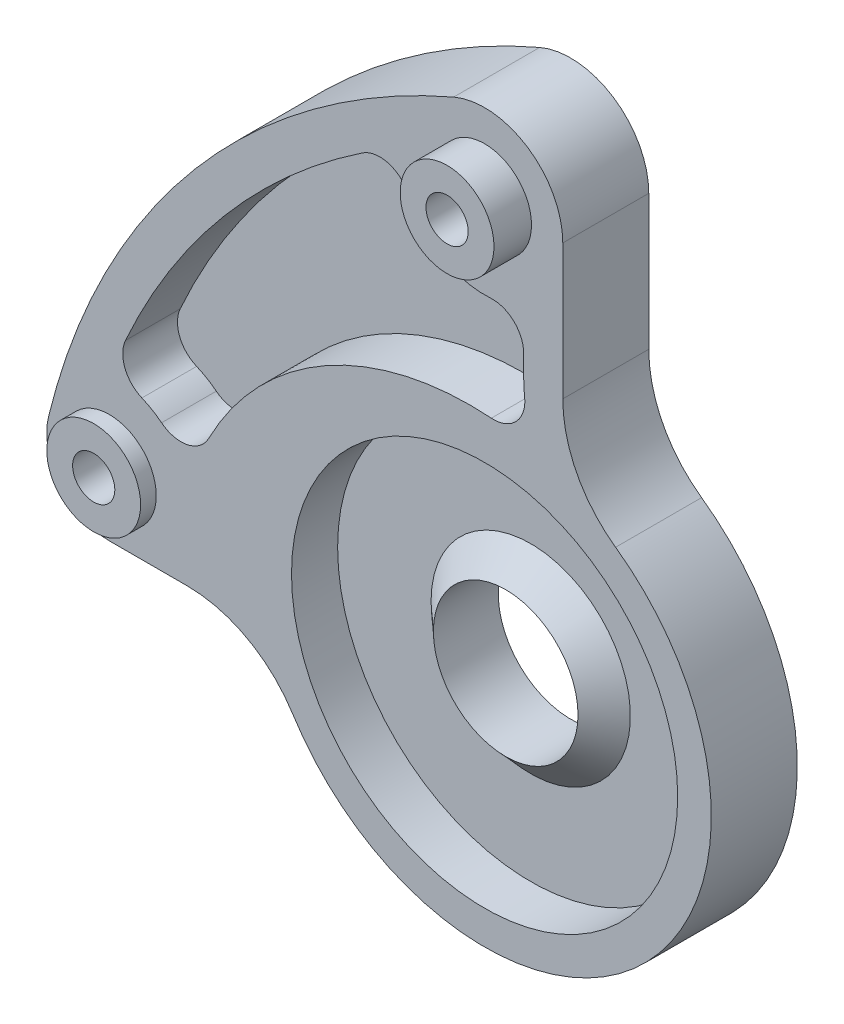
SolidWorks part; units mm, degrees
ref_plane "Front Plane" through (0, 0, 0) normal (0, 0, 1) x (1, 0, 0)
ref_plane "Top Plane" through (0, 0, 0) normal (0, 1, 0) x (1, 0, 0)
ref_plane "Right Plane" through (0, 0, 0) normal (1, 0, 0) x (0, 0, -1)
ref_plane "Plane1" through (0, 0, 5.5) normal (0, 0, 1) x (1, 0, 0)
sketch "Sketch1" plane through (0, 0, 5.5) normal (0, 0, 1) x (1, 0, 0)
  line L0 (5, 18.3644) -> (5, 27)
  line L1 (-24, -4) -> (-19.0329, -4)
  arc A0 (8.3778, 11.8348) -> (5, 18.3644) centre (13, 18.3644) cw
  arc A1 (5, 27) -> (-1.9784, 31.5919) centre (0, 27) ccw
  arc A2 (-1.9784, 31.5919) -> (-27.8856, 0.9498) centre (15.8274, -9.7355) ccw
  arc A3 (-27.8856, 0.9498) -> (-24, -4) centre (-24, 0) ccw
  arc A4 (-19.0329, -4) -> (-12.2656, -7.7333) centre (-19.0329, -12) cw
  arc A5 (-12.2656, -7.7333) -> (8.3778, 11.8348) centre (0, 0) ccw
extrude "Boss-Extrude1" add sketch "Sketch1" against normal blind 5.5
sketch "Sketch2" plane through (0, 0, 5.5) normal (0, 0, 1) x (1, 0, 0)
  circle A0 centre (0, 27) radius 3
  dimension "D1" = 6
extrude "Boss-Extrude2" add sketch "Sketch2" along normal blind 2.4
sketch "Sketch3" plane through (0, 0, 5.5) normal (0, 0, 1) x (1, 0, 0)
  circle A0 centre (-24, 0) radius 3
  dimension "D1" = 6
extrude "Boss-Extrude3" add sketch "Sketch3" along normal blind 1
sketch "Sketch4" plane through (0, 0, 0) normal (0, 0, -1) x (-1, 0, 0)
  circle A0 centre (0, 0) radius 4.625
  dimension "D1" = 9.25
extrude "Cut-Extrude1" cut sketch "Sketch4" against normal through all
sketch "Sketch5" plane through (0, 0, 7.9) normal (0, 0, 1) x (1, 0, 0)
  circle A0 centre (0, 27) radius 1.35
  circle A1 centre (-24, 0) radius 1.35
  dimension "D1" = 2.7
  dimension "D2" = 2.7
extrude "Cut-Extrude2" cut sketch "Sketch5" against normal through all
sketch "Sketch7" plane through (0, 0, 5.5) normal (0, 0, 1) x (1, 0, 0)
  circle A0 centre (0, 0) radius 12.35
  circle A1 centre (0, 0) radius 12.1 construction
  dimension "D1" = 0.25
  dimension "D2" = 24.2
extrude "Cut-Extrude4" cut sketch "Sketch7" against normal blind 2.95
sketch "Sketch8" plane through (0, 0, 5.5) normal (0, 0, 1) x (1, 0, 0)
  line L0 (2.5, 18.3644) -> (2.5, 19.6403)
  arc A0 (0.3644, 21.6357) -> (-4.8853, 24.7546) centre (0, 27) cw
  arc A1 (-4.8853, 24.7546) -> (-7.8152, 25.5814) centre (-6.7026, 23.9194) ccw
  arc A2 (-7.8152, 25.5814) -> (-22.9686, 7.6175) centre (15.8274, -9.7355) ccw
  arc A3 (-22.9686, 7.6175) -> (-21.9175, 4.957) centre (-21.1429, 6.8009) ccw
  arc A4 (-21.9175, 4.957) -> (-20.6588, 4.2124) centre (-24, 0) cw
  arc A5 (-20.6588, 4.2124) -> (-17.6384, 4.8627) centre (-19.4159, 5.7794) ccw
  arc A6 (-17.6384, 4.8627) -> (0.4318, 15.0138) centre (-0.9047, -3.7663) cw
  arc A7 (0.4318, 15.0138) -> (2.5619, 17.2256) centre (0.5737, 17.0087) ccw
  arc A8 (2.5619, 17.2256) -> (2.5, 18.3644) centre (13, 18.3644) cw
  arc A9 (2.5, 19.6403) -> (0.3644, 21.6357) centre (0.5, 19.6403) ccw
extrude "Cut-Extrude5" cut sketch "Sketch8" against normal blind 3.5
sketch "Sketch9" plane through (0, 0, 2.55) normal (0, 0, 1) x (1, 0, 0)
  circle A0 centre (0, 0) radius 4.625 construction
  circle A1 centre (0, 0) radius 4.625
  circle A3 centre (0, 0) radius 6.375
  dimension "D2" = 1.75
extrude "Boss-Extrude4" add sketch "Sketch9" along normal blind 1.6
chamfer "Chamfer1" distance 1.6 distance2 1.75 1 edges at (6.375, 0, 4.15) first distance on face at (6.375, 0, 4.15)
